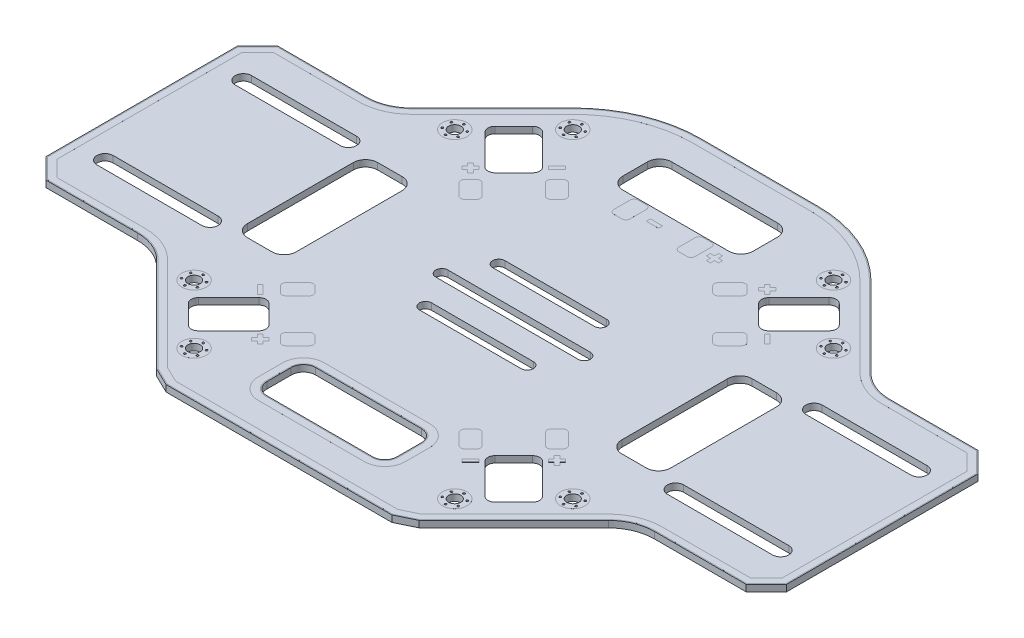
SolidWorks part; units mm, degrees
material "Baseplate Screw Material"
ref_plane "Front Plane" through (0, 0, 0) normal (0, 0, 1) x (1, 0, 0)
ref_plane "Top Plane" through (0, 0, 0) normal (0, 1, 0) x (1, 0, 0)
ref_plane "Right Plane" through (0, 0, 0) normal (1, 0, 0) x (0, 0, -1)
sketch "Sketch1" plane through (0, 0, 0) normal (0, 1, 0) x (1, 0, 0)
  line L0 (0, 60.3186) -> (0, -57.6814) construction
  line L1 (-27.75, -57.6814) -> (27.75, -57.6814)
  line L2 (-13, -47.6814) -> (13, -47.6814)
  line L3 (-16, -38.6814) -> (-16, -44.6814)
  line L4 (16, -38.6814) -> (16, -44.6814)
  line L5 (-16, -41.6814) -> (16, -41.6814) construction
  line L6 (-13, -35.6814) -> (13, -35.6814)
  line L7 (-27.75, -57.6814) -> (-32.25, -55.502)
  line L8 (27.75, -57.6814) -> (32.25, -55.502)
  line L9 (-32.25, -55.502) -> (32.25, -55.502) construction
  line L10 (32.25, -55.502) -> (55.502, -32.25)
  line L11 (-32.25, -55.502) -> (-55.502, -32.25)
  line L12 (-43.876, 43.876) -> (43.876, -43.876) construction
  line L13 (-43.876, -43.876) -> (43.876, 43.876) construction
  line L14 (37.6888, -42.285) -> (42.285, -37.6888)
  line L15 (27.7893, -34.8604) -> (35.2139, -42.285)
  line L16 (34.8604, -27.7893) -> (42.285, -35.2139)
  line L17 (31.5016, -38.5727) -> (38.5727, -31.5016) construction
  line L18 (27.7893, -32.3855) -> (32.3855, -27.7893)
  line L19 (-38.5727, -31.5016) -> (-31.5016, -38.5727) construction
  line L20 (-35.2139, -42.285) -> (-27.7893, -34.8604)
  line L21 (-42.285, -35.2139) -> (-34.8604, -27.7893)
  line L22 (-32.3855, -27.7893) -> (-27.7893, -32.3855)
  line L23 (-42.285, -37.6888) -> (-37.6888, -42.285)
  line L24 (-63.5, -28.9371) -> (63.5, -28.9371) construction
  line L25 (63.5, -28.9371) -> (86, -28.9371)
  line L26 (-63.5, -28.9371) -> (-86, -28.9371)
  line L27 (-91, -23.9371) -> (-91, 23.0629)
  line L28 (91, -23.9371) -> (91, 23.0629)
  line L29 (-86, -28.9371) -> (-86, 28.0629) construction
  line L30 (86, -28.9371) -> (86, 28.0629) construction
  line L31 (-91, -0.4371) -> (-86, -0.4371) construction
  line L32 (86, -0.4371) -> (91, -0.4371) construction
  line L33 (86, -28.9371) -> (91, -23.9371)
  line L34 (-91, -23.9371) -> (-86, -28.9371)
  line L35 (91, 23.0629) -> (86, 28.0629)
  line L36 (-91, 23.0629) -> (-86, 28.0629)
  line L37 (-56.4271, 31.3248) -> (-36.6281, 51.1238)
  line L38 (36.6281, 51.1238) -> (56.4271, 31.3248)
  line L39 (-35.2139, 42.285) -> (-27.7893, 34.8604)
  line L40 (-36.6281, 51.1238) -> (-27.7893, 42.285) construction
  line L41 (-27.7893, 42.285) -> (-31.5016, 38.5727) construction
  line L42 (-42.285, 35.2139) -> (-34.8604, 27.7893)
  line L43 (-31.5016, 38.5727) -> (-38.5727, 31.5016) construction
  line L44 (-42.285, 37.6888) -> (-37.6888, 42.285)
  line L45 (-32.3855, 27.7893) -> (-27.7893, 32.3855)
  line L46 (-86, 28.0629) -> (-64.3021, 28.0629)
  line L47 (86, 28.0629) -> (64.3021, 28.0629)
  line L48 (37.6888, 42.285) -> (42.285, 37.6888)
  line L49 (27.7893, 32.3855) -> (32.3855, 27.7893)
  line L50 (27.7893, 34.8604) -> (35.2139, 42.285)
  line L51 (34.8604, 27.7893) -> (42.285, 35.2139)
  line L52 (31.5016, 38.5727) -> (38.5727, 31.5016) construction
  line L53 (31.5016, 38.5727) -> (27.7893, 42.285) construction
  line L54 (27.7893, 42.285) -> (36.6281, 51.1238) construction
  line L55 (-14.43, 60.3186) -> (14.43, 60.3186)
  line L56 (-13, 51.8186) -> (13, 51.8186)
  line L57 (-13, 39.8186) -> (13, 39.8186)
  line L58 (16, 48.8186) -> (16, 42.8186)
  line L59 (-16, 48.8186) -> (-16, 42.8186)
  line L60 (-12.5, -10.6814) -> (12.5, -10.6814)
  line L61 (-12.5, -7.6814) -> (12.5, -7.6814)
  line L62 (-17.5, -1.6814) -> (17.5, -1.6814)
  line L63 (-17.5, 1.3186) -> (17.5, 1.3186)
  line L64 (-12.5, 7.3186) -> (12.5, 7.3186)
  line L65 (-12.5, 10.3186) -> (12.5, 10.3186)
  line L66 (-52, 12.5629) -> (-52, -13.4371)
  line L67 (-86, -0.4371) -> (-52, -0.4371) construction
  line L68 (-40, 12.5629) -> (-40, -13.4371)
  line L69 (52, 12.5629) -> (52, -13.4371)
  line L70 (-49, 15.5629) -> (-43, 15.5629)
  line L71 (-49, -16.4371) -> (-43, -16.4371)
  line L72 (86, -0.4371) -> (52, -0.4371) construction
  line L73 (40, 12.5629) -> (40, -13.4371)
  line L74 (43, 15.5629) -> (49, 15.5629)
  line L75 (43, -16.4371) -> (49, -16.4371)
  line L76 (-83, 18.5629) -> (-57.2, 18.5629)
  line L77 (-83, 14.5629) -> (-57.2, 14.5629)
  line L78 (-83, -15.4371) -> (-57.2, -15.4371)
  line L79 (-83, -19.4371) -> (-57.2, -19.4371)
  line L80 (57.2, -15.4371) -> (83, -15.4371)
  line L81 (57.2, -19.4371) -> (83, -19.4371)
  line L82 (57.2, 18.5629) -> (83, 18.5629)
  line L83 (57.2, 14.5629) -> (83, 14.5629)
  line L84 (-46.5276, 32.0319) -> (-32.0319, 46.5276) construction
  line L85 (32.0319, -46.5276) -> (46.5276, -32.0319) construction
  arc A0 (-16, -44.6814) -> (-13, -47.6814) centre (-13, -44.6814) ccw
  arc A1 (-13, -35.6814) -> (-16, -38.6814) centre (-13, -38.6814) ccw
  arc A2 (16, -38.6814) -> (13, -35.6814) centre (13, -38.6814) ccw
  arc A3 (13, -47.6814) -> (16, -44.6814) centre (13, -44.6814) ccw
  arc A4 (27.7893, -32.3855) -> (27.7893, -34.8604) centre (29.0267, -33.6229) ccw
  arc A5 (34.8604, -27.7893) -> (32.3855, -27.7893) centre (33.6229, -29.0267) ccw
  arc A6 (35.2139, -42.285) -> (37.6888, -42.285) centre (36.4514, -41.0475) ccw
  arc A7 (42.285, -37.6888) -> (42.285, -35.2139) centre (41.0475, -36.4514) ccw
  arc A8 (-37.6888, -42.285) -> (-35.2139, -42.285) centre (-36.4514, -41.0475) ccw
  arc A9 (-42.285, -35.2139) -> (-42.285, -37.6888) centre (-41.0475, -36.4514) ccw
  arc A10 (-32.3855, -27.7893) -> (-34.8604, -27.7893) centre (-33.6229, -29.0267) ccw
  arc A11 (-27.7893, -34.8604) -> (-27.7893, -32.3855) centre (-29.0267, -33.6229) ccw
  arc A12 (-55.502, -32.25) -> (-63.5, -28.9371) centre (-63.5, -40.248) ccw
  arc A13 (63.5, -28.9371) -> (55.502, -32.25) centre (63.5, -40.248) ccw
  arc A14 (-42.285, 37.6888) -> (-42.285, 35.2139) centre (-41.0475, 36.4514) ccw
  arc A15 (-35.2139, 42.285) -> (-37.6888, 42.285) centre (-36.4514, 41.0475) ccw
  arc A16 (-27.7893, 32.3855) -> (-27.7893, 34.8604) centre (-29.0267, 33.6229) ccw
  arc A17 (-34.8604, 27.7893) -> (-32.3855, 27.7893) centre (-33.6229, 29.0267) ccw
  arc A18 (-64.3021, 28.0629) -> (-56.4271, 31.3248) centre (-64.3021, 39.1998) ccw
  arc A19 (56.4271, 31.3248) -> (64.3021, 28.0629) centre (64.3021, 39.1998) ccw
  arc A20 (27.7893, 34.8604) -> (27.7893, 32.3855) centre (29.0267, 33.6229) ccw
  arc A21 (37.6888, 42.285) -> (35.2139, 42.285) centre (36.4514, 41.0475) ccw
  arc A22 (42.285, 35.2139) -> (42.285, 37.6888) centre (41.0475, 36.4514) ccw
  arc A23 (32.3855, 27.7893) -> (34.8604, 27.7893) centre (33.6229, 29.0267) ccw
  arc A24 (-14.43, 60.3186) -> (-36.6281, 51.1238) centre (-14.43, 28.9257) ccw
  arc A25 (13, 39.8186) -> (16, 42.8186) centre (13, 42.8186) ccw
  arc A26 (36.6281, 51.1238) -> (14.43, 60.3186) centre (14.43, 28.9257) ccw
  arc A27 (16, 48.8186) -> (13, 51.8186) centre (13, 48.8186) ccw
  arc A28 (-16, 42.8186) -> (-13, 39.8186) centre (-13, 42.8186) ccw
  arc A29 (-13, 51.8186) -> (-16, 48.8186) centre (-13, 48.8186) ccw
  arc A30 (-12.5, -7.6814) -> (-12.5, -10.6814) centre (-12.5, -9.1814) ccw
  arc A31 (12.5, -10.6814) -> (12.5, -7.6814) centre (12.5, -9.1814) ccw
  arc A32 (-17.5, 1.3186) -> (-17.5, -1.6814) centre (-17.5, -0.1814) ccw
  arc A33 (17.5, -1.6814) -> (17.5, 1.3186) centre (17.5, -0.1814) ccw
  arc A34 (-12.5, 10.3186) -> (-12.5, 7.3186) centre (-12.5, 8.8186) ccw
  arc A35 (12.5, 7.3186) -> (12.5, 10.3186) centre (12.5, 8.8186) ccw
  arc A36 (-49, 15.5629) -> (-52, 12.5629) centre (-49, 12.5629) ccw
  arc A37 (-40, 12.5629) -> (-43, 15.5629) centre (-43, 12.5629) ccw
  arc A38 (-52, -13.4371) -> (-49, -16.4371) centre (-49, -13.4371) ccw
  arc A39 (-43, -16.4371) -> (-40, -13.4371) centre (-43, -13.4371) ccw
  arc A40 (43, 15.5629) -> (40, 12.5629) centre (43, 12.5629) ccw
  arc A41 (52, 12.5629) -> (49, 15.5629) centre (49, 12.5629) ccw
  arc A42 (40, -13.4371) -> (43, -16.4371) centre (43, -13.4371) ccw
  arc A43 (49, -16.4371) -> (52, -13.4371) centre (49, -13.4371) ccw
  arc A44 (-57.2, 14.5629) -> (-57.2, 18.5629) centre (-57.2, 16.5629) ccw
  arc A45 (-83, 18.5629) -> (-83, 14.5629) centre (-83, 16.5629) ccw
  arc A46 (-83, -15.4371) -> (-83, -19.4371) centre (-83, -17.4371) ccw
  arc A47 (-57.2, -19.4371) -> (-57.2, -15.4371) centre (-57.2, -17.4371) ccw
  arc A48 (57.2, -15.4371) -> (57.2, -19.4371) centre (57.2, -17.4371) ccw
  arc A49 (83, -19.4371) -> (83, -15.4371) centre (83, -17.4371) ccw
  arc A50 (57.2, 18.5629) -> (57.2, 14.5629) centre (57.2, 16.5629) ccw
  arc A51 (83, 14.5629) -> (83, 18.5629) centre (83, 16.5629) ccw
  circle A52 centre (-32.0319, 46.5276) radius 1.5
  circle A53 centre (-46.5276, 32.0319) radius 1.5
  circle A54 centre (32.0319, -46.5276) radius 1.5
  circle A55 centre (46.5276, -32.0319) radius 1.5
  circle A56 centre (-46.5276, -32.0319) radius 1.5
  circle A57 centre (-32.0319, -46.5276) radius 1.5
  circle A58 centre (32.0319, 46.5276) radius 1.5
  circle A59 centre (46.5276, 32.0319) radius 1.5
  point P4 (-35.0371, 35.0371)
  point P5 (0, -47.6814)
  point P14 (0, -41.6814)
  point P15 (0, -35.6814)
  point P19 (0, -55.502)
  point P29 (0, 0)
  point P30 (39.9869, -39.9869)
  point P32 (0, 0)
  point P42 (30.0874, -30.0874)
  point P43 (35.0371, -35.0371)
  point P50 (-35.0371, -35.0371)
  point P53 (-38.5727, -31.5016)
  point P62 (-39.9869, -39.9869)
  point P63 (-30.0874, -30.0874)
  point P70 (0, -28.9371)
  point P99 (-39.9869, 39.9869)
  point P102 (-30.0874, 30.0874)
  point P119 (35.0371, 35.0371)
  point P122 (39.9869, 39.9869)
  point P123 (30.0874, 30.0874)
  point P135 (0, 51.8186)
  point P138 (0, 39.8186)
  point P147 (0, -10.6814)
  point P151 (-14, -9.1814)
  point P153 (14, -9.1814)
  point P156 (0, -1.6814)
  point P158 (-19, -0.1814)
  point P162 (19, -0.1814)
  point P167 (0, 7.3186)
  point P203 (-85, 16.5629)
  point P205 (-55.2, 16.5629)
  point P217 (85, -17.4371)
  point P229 (-39.2798, 39.2798)
  point P232 (39.2798, -39.2798)
  dimension "D5" = 12
  dimension "D6" = 55.5
  dimension "D14" = 14
  dimension "D15" = 127
  dimension "D16" = 22.5
  dimension "D23" = 8.5
  dimension "D24" = 25
  dimension "D25" = 3
  dimension "D28" = 3
  dimension "D31" = 39
  dimension "D32" = 9.5
  dimension "D34" = 29.8
  dimension "D38" = 6
  dimension "D39" = 3
  dimension "D1" = 118
  dimension "D2" = 10
  dimension "D3" = 32
  dimension "D4" = 6
  dimension "D7" = 64.5
  dimension "D8" = 5
  dimension "D9" = 124.1
  dimension "D10" = 45
  dimension "D11" = 5.5
  dimension "D12" = 6.5
  dimension "D13" = 10
  dimension "D17" = 22.5
  dimension "D18" = 5
  dimension "D19" = 45
  dimension "D20" = 47
  dimension "D21" = 28
  dimension "D22" = 5.25
  dimension "D26" = 28
  dimension "D27" = 6
  dimension "D29" = 38
  dimension "D30" = 6
  dimension "D33" = 4
  dimension "D35" = 6
  dimension "D36" = 9.5
  dimension "D37" = 4
  dimension "D40" = 6.5
  dimension "D41" = 6.5
extrude "Boss-Extrude1" add sketch "Sketch1" along normal blind 0.8 and the other way blind 0.8
sketch "Sketch2" plane through (0, 0.8, 0) normal (0, 1, 0) x (1, 0, 0)
  line L0 (-27.6926, -57.4314) -> (27.6926, -57.4314)
  line L1 (-27.75, -57.6814) -> (27.75, -57.6814) construction
  line L2 (-27.6926, -57.4314) -> (-32.1031, -55.2953)
  line L3 (-32.25, -55.502) -> (-27.75, -57.6814) construction
  line L4 (27.6926, -57.4314) -> (32.1031, -55.2953)
  line L5 (27.75, -57.6814) -> (32.25, -55.502) construction
  line L6 (0, -57.6814) -> (0, -57.4314) construction
  line L7 (-32.1031, -55.2953) -> (-55.3252, -32.0732)
  line L8 (-55.502, -32.25) -> (-32.25, -55.502) construction
  line L9 (32.1031, -55.2953) -> (55.3252, -32.0732)
  line L10 (32.25, -55.502) -> (55.502, -32.25) construction
  line L11 (-85.8964, -28.6871) -> (-63.5, -28.6871)
  line L12 (-85.8964, -28.6871) -> (-90.75, -23.8335)
  line L13 (-91, -23.9371) -> (-86, -28.9371) construction
  line L14 (-86, -28.9371) -> (-63.5, -28.9371) construction
  line L15 (63.5, -28.6871) -> (85.8964, -28.6871)
  line L16 (85.8964, -28.6871) -> (90.75, -23.8335)
  line L17 (-90.75, -23.8335) -> (-90.75, 22.9593)
  line L18 (-91, 23.0629) -> (-91, -23.9371) construction
  line L19 (-90.75, 22.9593) -> (-85.8964, 27.8129)
  line L20 (-85.8964, 27.8129) -> (-64.3021, 27.8129)
  line L21 (-64.3021, 28.0629) -> (-86, 28.0629) construction
  line L22 (-56.2503, 31.1481) -> (-36.4514, 50.947)
  line L23 (-36.6281, 51.1238) -> (-56.4271, 31.3248) construction
  line L24 (-14.43, 60.0686) -> (14.43, 60.0686)
  line L25 (14.43, 60.3186) -> (-14.43, 60.3186) construction
  line L26 (56.2503, 31.1481) -> (36.4514, 50.947)
  line L27 (56.4271, 31.3248) -> (36.6281, 51.1238) construction
  line L28 (64.3021, 27.8129) -> (85.8964, 27.8129)
  line L29 (86, 28.0629) -> (64.3021, 28.0629) construction
  line L30 (85.8964, 27.8129) -> (90.75, 22.9593)
  line L31 (91, 23.0629) -> (86, 28.0629) construction
  line L32 (90.75, 22.9593) -> (90.75, -23.8335)
  line L33 (-55.0836, 29.9813) -> (-35.2846, 49.7803)
  line L34 (-14.43, 58.4186) -> (14.43, 58.4186)
  line L35 (55.0836, 29.9813) -> (35.2846, 49.7803)
  line L36 (64.3021, 26.1629) -> (85.213, 26.1629)
  line L37 (85.213, 26.1629) -> (89.1, 22.2759)
  line L38 (89.1, 22.2759) -> (89.1, -23.1501)
  line L39 (85.213, -27.0371) -> (89.1, -23.1501)
  line L40 (63.5, -27.0371) -> (85.213, -27.0371)
  line L41 (31.1332, -53.9317) -> (54.1584, -30.9065)
  line L42 (27.3141, -55.7814) -> (31.1332, -53.9317)
  line L43 (-27.3141, -55.7814) -> (27.3141, -55.7814)
  line L44 (-27.3141, -55.7814) -> (-31.1332, -53.9317)
  line L45 (-31.1332, -53.9317) -> (-54.1584, -30.9065)
  line L46 (-85.213, -27.0371) -> (-63.5, -27.0371)
  line L47 (-85.213, -27.0371) -> (-89.1, -23.1501)
  line L48 (-89.1, -23.1501) -> (-89.1, 22.2759)
  line L49 (-89.1, 22.2759) -> (-85.213, 26.1629)
  line L50 (-85.213, 26.1629) -> (-64.3021, 26.1629)
  line L51 (-13, -35.4314) -> (13, -35.4314)
  line L52 (-16.25, -38.6814) -> (-16.25, -44.6814)
  line L53 (-13, -47.9314) -> (13, -47.9314)
  line L54 (16.25, -44.6814) -> (16.25, -38.6814)
  line L55 (16, -44.6814) -> (16, -38.6814) construction
  line L56 (13, -35.6814) -> (-13, -35.6814) construction
  line L57 (-16, -38.6814) -> (-16, -44.6814) construction
  line L58 (-13, -47.6814) -> (13, -47.6814) construction
  line L59 (-13, -33.6314) -> (13, -33.6314)
  line L60 (18.05, -44.6814) -> (18.05, -38.6814)
  line L61 (-13, -49.7314) -> (13, -49.7314)
  line L62 (-18.05, -38.6814) -> (-18.05, -44.6814)
  line L63 (32.0319, -43.5276) -> (32.0319, -44.2776) construction
  line L64 (-32.0319, -44.2776) -> (-33.9805, -45.4026) construction
  line L65 (-33.9805, -45.4026) -> (-33.9805, -47.6526) construction
  line L66 (-33.9805, -47.6526) -> (-32.0319, -48.7776) construction
  line L67 (-32.0319, -48.7776) -> (-30.0834, -47.6526) construction
  line L68 (-30.0834, -47.6526) -> (-30.0834, -45.4026) construction
  line L69 (-30.0834, -45.4026) -> (-32.0319, -44.2776) construction
  line L70 (-46.5276, -29.7819) -> (-48.4762, -30.9069) construction
  line L71 (-48.4762, -30.9069) -> (-48.4762, -33.1569) construction
  line L72 (-48.4762, -33.1569) -> (-46.5276, -34.2819) construction
  line L73 (-46.5276, -34.2819) -> (-44.5791, -33.1569) construction
  line L74 (-44.5791, -33.1569) -> (-44.5791, -30.9069) construction
  line L75 (-44.5791, -30.9069) -> (-46.5276, -29.7819) construction
  line L76 (-46.5276, 34.2819) -> (-48.4762, 33.1569) construction
  line L77 (-48.4762, 33.1569) -> (-48.4762, 30.9069) construction
  line L78 (-48.4762, 30.9069) -> (-46.5276, 29.7819) construction
  line L79 (-46.5276, 29.7819) -> (-44.5791, 30.9069) construction
  line L80 (-44.5791, 30.9069) -> (-44.5791, 33.1569) construction
  line L81 (-44.5791, 33.1569) -> (-46.5276, 34.2819) construction
  line L82 (-32.0319, 48.7776) -> (-33.9805, 47.6526) construction
  line L83 (-33.9805, 47.6526) -> (-33.9805, 45.4026) construction
  line L84 (-33.9805, 45.4026) -> (-32.0319, 44.2776) construction
  line L85 (-32.0319, 44.2776) -> (-30.0834, 45.4026) construction
  line L86 (-30.0834, 45.4026) -> (-30.0834, 47.6526) construction
  line L87 (-30.0834, 47.6526) -> (-32.0319, 48.7776) construction
  line L88 (32.0319, 48.7776) -> (30.0834, 47.6526) construction
  line L89 (30.0834, 47.6526) -> (30.0834, 45.4026) construction
  line L90 (30.0834, 45.4026) -> (32.0319, 44.2776) construction
  line L91 (32.0319, 44.2776) -> (33.9805, 45.4026) construction
  line L92 (33.9805, 45.4026) -> (33.9805, 47.6526) construction
  line L93 (33.9805, 47.6526) -> (32.0319, 48.7776) construction
  line L94 (46.5276, 34.2819) -> (44.5791, 33.1569) construction
  line L95 (44.5791, 33.1569) -> (44.5791, 30.9069) construction
  line L96 (44.5791, 30.9069) -> (46.5276, 29.7819) construction
  line L97 (46.5276, 29.7819) -> (48.4762, 30.9069) construction
  line L98 (48.4762, 30.9069) -> (48.4762, 33.1569) construction
  line L99 (48.4762, 33.1569) -> (46.5276, 34.2819) construction
  line L100 (46.5276, -29.7819) -> (44.5791, -30.9069) construction
  line L101 (44.5791, -30.9069) -> (44.5791, -33.1569) construction
  line L102 (44.5791, -33.1569) -> (46.5276, -34.2819) construction
  line L103 (46.5276, -34.2819) -> (48.4762, -33.1569) construction
  line L104 (48.4762, -33.1569) -> (48.4762, -30.9069) construction
  line L105 (48.4762, -30.9069) -> (46.5276, -29.7819) construction
  line L106 (32.0319, -44.2776) -> (30.0834, -45.4026) construction
  line L107 (30.0834, -45.4026) -> (30.0834, -47.6526) construction
  line L108 (30.0834, -47.6526) -> (32.0319, -48.7776) construction
  line L109 (32.0319, -48.7776) -> (33.9805, -47.6526) construction
  line L110 (33.9805, -47.6526) -> (33.9805, -45.4026) construction
  line L111 (33.9805, -45.4026) -> (32.0319, -44.2776) construction
  line L112 (32.0319, -44.2776) -> (32.0319, -45.0276) construction
  arc A0 (-55.3252, -32.0732) -> (-63.5, -28.6871) centre (-63.5, -40.248) ccw
  arc A1 (-55.502, -32.25) -> (-63.5, -28.9371) centre (-63.5, -40.248) ccw construction
  arc A2 (63.5, -28.6871) -> (55.3252, -32.0732) centre (63.5, -40.248) ccw
  arc A3 (63.5, -28.9371) -> (55.502, -32.25) centre (63.5, -40.248) ccw construction
  arc A4 (-64.3021, 27.8129) -> (-56.2503, 31.1481) centre (-64.3021, 39.1998) ccw
  arc A5 (-64.3021, 28.0629) -> (-56.4271, 31.3248) centre (-64.3021, 39.1998) ccw construction
  arc A6 (-14.43, 60.0686) -> (-36.4514, 50.947) centre (-14.43, 28.9257) ccw
  arc A7 (-14.43, 60.3186) -> (-36.6281, 51.1238) centre (-14.43, 28.9257) ccw construction
  arc A8 (36.4514, 50.947) -> (14.43, 60.0686) centre (14.43, 28.9257) ccw
  arc A9 (36.6281, 51.1238) -> (14.43, 60.3186) centre (14.43, 28.9257) ccw construction
  arc A10 (56.2503, 31.1481) -> (64.3021, 27.8129) centre (64.3021, 39.1998) ccw
  arc A11 (56.4271, 31.3248) -> (64.3021, 28.0629) centre (64.3021, 39.1998) ccw construction
  arc A12 (-14.43, 58.4186) -> (-35.2846, 49.7803) centre (-14.43, 28.9257) ccw
  arc A13 (35.2846, 49.7803) -> (14.43, 58.4186) centre (14.43, 28.9257) ccw
  arc A14 (55.0836, 29.9813) -> (64.3021, 26.1629) centre (64.3021, 39.1998) ccw
  arc A15 (63.5, -27.0371) -> (54.1584, -30.9065) centre (63.5, -40.248) ccw
  arc A16 (-54.1584, -30.9065) -> (-63.5, -27.0371) centre (-63.5, -40.248) ccw
  arc A17 (-64.3021, 26.1629) -> (-55.0836, 29.9813) centre (-64.3021, 39.1998) ccw
  arc A18 (-13, -35.4314) -> (-16.25, -38.6814) centre (-13, -38.6814) ccw
  arc A19 (16.25, -38.6814) -> (13, -35.4314) centre (13, -38.6814) ccw
  arc A20 (-16.25, -44.6814) -> (-13, -47.9314) centre (-13, -44.6814) ccw
  arc A21 (13, -47.9314) -> (16.25, -44.6814) centre (13, -44.6814) ccw
  arc A22 (-13, -35.6814) -> (-16, -38.6814) centre (-13, -38.6814) ccw construction
  arc A23 (-16, -44.6814) -> (-13, -47.6814) centre (-13, -44.6814) ccw construction
  arc A24 (16, -38.6814) -> (13, -35.6814) centre (13, -38.6814) ccw construction
  arc A25 (13, -47.6814) -> (16, -44.6814) centre (13, -44.6814) ccw construction
  arc A26 (18.05, -38.6814) -> (13, -33.6314) centre (13, -38.6814) ccw
  arc A27 (13, -49.7314) -> (18.05, -44.6814) centre (13, -44.6814) ccw
  arc A28 (-18.05, -44.6814) -> (-13, -49.7314) centre (-13, -44.6814) ccw
  arc A29 (-13, -33.6314) -> (-18.05, -38.6814) centre (-13, -38.6814) ccw
  circle A30 centre (-32.0319, -46.5276) radius 1.5
  circle A31 centre (-46.5276, -32.0319) radius 1.5
  circle A32 centre (-46.5276, 32.0319) radius 1.5
  circle A33 centre (-32.0319, 46.5276) radius 1.5
  circle A34 centre (32.0319, 46.5276) radius 1.5
  circle A35 centre (46.5276, 32.0319) radius 1.5
  circle A36 centre (46.5276, -32.0319) radius 1.5
  circle A37 centre (32.0319, -46.5276) radius 1.5
  circle A38 centre (-32.0319, -46.5276) radius 1.5 construction
  circle A39 centre (-46.5276, -32.0319) radius 1.5 construction
  circle A40 centre (-46.5276, 32.0319) radius 1.5 construction
  circle A41 centre (-32.0319, 46.5276) radius 1.5 construction
  circle A42 centre (32.0319, 46.5276) radius 1.5 construction
  circle A43 centre (46.5276, 32.0319) radius 1.5 construction
  circle A44 centre (46.5276, -32.0319) radius 1.5 construction
  circle A45 centre (32.0319, -46.5276) radius 1.5 construction
  circle A46 centre (-32.0319, -46.5276) radius 3
  circle A47 centre (-46.5276, -32.0319) radius 3
  circle A48 centre (-46.5276, 32.0319) radius 3
  circle A49 centre (-32.0319, 46.5276) radius 3
  circle A50 centre (32.0319, 46.5276) radius 3
  circle A51 centre (46.5276, 32.0319) radius 3
  circle A52 centre (46.5276, -32.0319) radius 3
  circle A53 centre (32.0319, -46.5276) radius 3
  circle A54 centre (-32.0319, -46.5276) radius 1.9486 construction
  circle A55 centre (-46.5276, -32.0319) radius 1.9486 construction
  circle A56 centre (-46.5276, 32.0319) radius 1.9486 construction
  circle A57 centre (-32.0319, 46.5276) radius 1.9486 construction
  circle A58 centre (32.0319, 46.5276) radius 1.9486 construction
  circle A59 centre (46.5276, 32.0319) radius 1.9486 construction
  circle A60 centre (46.5276, -32.0319) radius 1.9486 construction
  circle A61 centre (32.0319, -46.5276) radius 1.9486 construction
  circle A62 centre (32.0319, -44.2776) radius 0.25
  circle A63 centre (33.9805, -45.4026) radius 0.25
  circle A64 centre (33.9805, -47.6526) radius 0.25
  circle A65 centre (32.0319, -48.7776) radius 0.25
  circle A66 centre (30.0834, -47.6526) radius 0.25
  circle A67 centre (30.0834, -45.4026) radius 0.25
  circle A68 centre (46.5276, -34.2819) radius 0.25
  circle A69 centre (48.4762, -33.1569) radius 0.25
  circle A70 centre (48.4762, -30.9069) radius 0.25
  circle A71 centre (46.5276, -29.7819) radius 0.25
  circle A72 centre (44.5791, -30.9069) radius 0.25
  circle A73 centre (44.5791, -33.1569) radius 0.25
  circle A74 centre (46.5276, 29.7819) radius 0.25
  circle A75 centre (48.4762, 30.9069) radius 0.25
  circle A76 centre (48.4762, 33.1569) radius 0.25
  circle A77 centre (46.5276, 34.2819) radius 0.25
  circle A78 centre (44.5791, 33.1569) radius 0.25
  circle A79 centre (44.5791, 30.9069) radius 0.25
  circle A80 centre (32.0319, 44.2776) radius 0.25
  circle A81 centre (33.9805, 45.4026) radius 0.25
  circle A82 centre (33.9805, 47.6526) radius 0.25
  circle A83 centre (32.0319, 48.7776) radius 0.25
  circle A84 centre (30.0834, 47.6526) radius 0.25
  circle A85 centre (30.0834, 45.4026) radius 0.25
  circle A86 centre (-32.0319, 48.7776) radius 0.25
  circle A87 centre (-30.0834, 47.6526) radius 0.25
  circle A88 centre (-30.0834, 45.4026) radius 0.25
  circle A89 centre (-32.0319, 44.2776) radius 0.25
  circle A90 centre (-33.9805, 47.6526) radius 0.25
  circle A91 centre (-33.9805, 45.4026) radius 0.25
  circle A92 centre (-46.5276, 29.7819) radius 0.25
  circle A93 centre (-44.5791, 30.9069) radius 0.25
  circle A94 centre (-44.5791, 33.1569) radius 0.25
  circle A95 centre (-46.5276, 34.2819) radius 0.25
  circle A96 centre (-48.4762, 33.1569) radius 0.25
  circle A97 centre (-48.4762, 30.9069) radius 0.25
  circle A98 centre (-46.5276, -29.7819) radius 0.25
  circle A99 centre (-44.5791, -30.9069) radius 0.25
  circle A100 centre (-44.5791, -33.1569) radius 0.25
  circle A101 centre (-46.5276, -34.2819) radius 0.25
  circle A102 centre (-48.4762, -33.1569) radius 0.25
  circle A103 centre (-48.4762, -30.9069) radius 0.25
  circle A104 centre (-32.0319, -44.2776) radius 0.25
  circle A105 centre (-30.0834, -45.4026) radius 0.25
  circle A106 centre (-30.0834, -47.6526) radius 0.25
  circle A107 centre (-32.0319, -48.7776) radius 0.25
  circle A108 centre (-33.9805, -47.6526) radius 0.25
  circle A109 centre (-33.9805, -45.4026) radius 0.25
  dimension "D2" = 0.25
  dimension "D5" = 0.25
  dimension "D7" = 1.65
  dimension "D8" = 0.25
  dimension "D10" = 6
  dimension "D11" = 0.5
  dimension "D1" = 0.25
  dimension "D3" = 0.25
  dimension "D4" = 0.25
  dimension "D6" = 0.25
  dimension "D9" = 1.8
extrude "Boss-Extrude2" add sketch "Sketch2" along normal blind 0.001 contours A10 L26 A8 L24 A6 L22 A4 L20 L19 L17 L12 L11 A0 L7 L2 L0 L4 L9 A2 L15 L16 L32 L30 L28 L50 A17 L33 A12 L34 A13 L35 A14 L36 L37 L38 L39 L40 A15 L41 L42 L43 L44 L45 A16 L46 L47 L48 L49 | A46 A109 A108 A107 A106 A105 A104 A30 | A47 A103 A102 A101 A100 A99 A98 A31 | A48 A97 A96 A95 A94 A93 A92 A32 | A49 A91 A90 A89 A88 A87 A86 A33 | A50 A85 A84 A83 A82 A81 A80 A34 | A51 A79 A78 A77 A76 A75 A74 A35 | A52 A73 A72 A71 A70 A69 A68 A36 | A53 A67 A66 A65 A64 A63 A62 A37 | L59 A29 L62 A28 L61 A27 L60 A26 A21 L53 A20 L52 A18 L51 A19 L54 region at (-29.8036, 0.8, 56.1688) region at (0, 0.8, 34.0267) region at (-34.9471, 0.8, 46.5276) region at (-49.4428, 0.8, 32.0319) region at (-49.4428, 0.8, -32.0319) region at (-34.9471, 0.8, -46.5276) region at (29.1168, 0.8, -46.5276) region at (43.6125, 0.8, -32.0319) region at (43.6125, 0.8, 32.0319) region at (29.1168, 0.8, 46.5276)
mirror "Mirror1" about plane through (0, 0, 0) normal (0, 1, 0) of "Boss-Extrude2"
sketch "Sketch3" plane through (0, -0.8, 0) normal (0, -1, 0) x (1, 0, 0)
  line L0 (0, 49.7314) -> (0, 51.7314) construction
  line L1 (-13, 49.7314) -> (13, 49.7314) construction
  line L2 (-27.3141, 55.7814) -> (27.3141, 55.7814) construction
  line L3 (11, 51.7314) -> (-11, 51.7314) construction
  line L4 (11, 53.7814) -> (-11, 53.7814) construction
  line L5 (0, 53.7814) -> (0, 55.7814) construction
  line L6 (11, 51.7314) -> (11, 53.7814) construction
  line L7 (-11, 51.7314) -> (-11, 53.7814) construction
  line L8 (11.29, 53.7814) -> (-10.71, 53.7814) construction
  text T0 "<b>DJI INNOVATIONS</b>" font "@Adobe Heiti Std R" height 2.05
  point P8 (0, 51.7314)
  point P11 (0, 53.7814)
  dimension "D1" = 2
  dimension "D2" = 22
  dimension "D3" = 0.29
extrude "Boss-Extrude3" add sketch "Sketch3" along normal blind 0.001
sketch "Sketch4" plane through (0, -0.8, 0) normal (0, -1, 0) x (1, 0, 0)
  line L0 (9.1282, 51.7314) -> (9.1282, 51.9909)
  line L1 (9.1282, 51.9909) -> (8.7389, 51.9909)
  line L2 (8.7389, 51.9909) -> (8.7389, 51.7314)
  line L3 (9.1282, 51.7314) -> (8.4275, 51.7314) construction
  line L4 (8.7389, 51.7314) -> (9.1282, 51.7314)
  line L6 (-3.2442, 51.7314) -> (-3.2442, 52.0168)
  line L7 (-3.2442, 52.0168) -> (-3.3442, 52.0168)
  line L8 (-3.893, 52.0168) -> (-3.2442, 52.0168) construction
  line L9 (-3.3442, 52.0168) -> (-3.3442, 51.7314)
  line L10 (-3.2442, 51.7314) -> (-4.8531, 51.7314) construction
  line L11 (-3.3442, 51.7314) -> (-3.2442, 51.7314)
  line L12 (-4.8531, 51.7314) -> (-4.7531, 51.7314)
  line L13 (-4.7531, 51.7314) -> (-4.7531, 52.0168)
  line L14 (-4.8531, 52.0168) -> (-4.2044, 52.0168) construction
  line L15 (-4.7531, 52.0168) -> (-4.8531, 52.0168)
  line L16 (-4.8531, 52.0168) -> (-4.8531, 51.7314)
  dimension "D1" = 0.1
extrude "Cut-Extrude1" cut sketch "Sketch4" along normal up to surface (0.001 mm away) up to face at (8.9409, -0.801, 52.931)
sketch "Sketch5" plane through (0, 0.8, 0) normal (0, 1, 0) x (1, 0, 0)
  line L0 (35.7442, -27.259) -> (36.4514, -26.5519)
  line L1 (35.0371, -26.5519) -> (35.7442, -25.8448)
  line L2 (35.3907, -26.9054) -> (37.512, -24.7841) construction
  line L3 (35.0371, -26.5519) -> (35.7442, -27.259)
  line L4 (37.1585, -24.4305) -> (37.8656, -25.1376)
  line L5 (42.285, -35.2139) -> (34.8604, -27.7893) construction
  line L6 (32.1031, -55.2953) -> (55.3252, -32.0732) construction
  line L8 (35.3907, -24.7841) -> (37.512, -26.9054) construction
  line L9 (35.0371, -25.1376) -> (35.7442, -24.4305)
  line L10 (37.1585, -27.259) -> (37.8656, -26.5519)
  line L11 (35.0371, -25.1376) -> (35.7442, -25.8448)
  line L12 (35.7442, -24.4305) -> (36.4514, -25.1376)
  line L13 (36.4514, -26.5519) -> (37.1585, -27.259)
  line L14 (36.4514, -25.1376) -> (37.1585, -24.4305)
  line L15 (37.1585, -25.8448) -> (37.8656, -26.5519)
  line L16 (37.1585, -25.8448) -> (37.8656, -25.1376)
  line L17 (26.9054, -35.3907) -> (24.7841, -37.512) construction
  line L18 (26.5519, -35.0371) -> (27.259, -35.7442)
  line L19 (27.7893, -34.8604) -> (35.2139, -42.285) construction
  line L20 (24.4305, -37.1585) -> (25.1376, -37.8656)
  line L21 (24.4305, -37.1585) -> (26.5519, -35.0371)
  line L22 (25.1376, -37.8656) -> (27.259, -35.7442)
  line L23 (-37.1585, -24.4305) -> (-37.8656, -25.1376)
  line L24 (-37.1585, -24.4305) -> (-35.0371, -26.5519)
  line L25 (-37.8656, -25.1376) -> (-35.7442, -27.259)
  line L26 (-35.3907, -26.9054) -> (-37.512, -24.7841) construction
  line L27 (-35.0371, -26.5519) -> (-35.7442, -27.259)
  line L28 (-26.5519, -35.0371) -> (-27.259, -35.7442)
  line L29 (-27.259, -35.7442) -> (-26.5519, -36.4514)
  line L30 (-26.5519, -36.4514) -> (-27.259, -37.1585)
  line L31 (-27.259, -37.1585) -> (-26.5519, -37.8656)
  line L32 (-25.8448, -37.1585) -> (-26.5519, -37.8656)
  line L33 (-25.8448, -37.1585) -> (-25.1376, -37.8656)
  line L34 (-24.4305, -37.1585) -> (-25.1376, -37.8656)
  line L35 (-25.1376, -36.4514) -> (-24.4305, -37.1585)
  line L36 (-24.4305, -35.7442) -> (-25.1376, -36.4514)
  line L37 (-25.1376, -35.0371) -> (-24.4305, -35.7442)
  line L38 (-25.1376, -35.0371) -> (-25.8448, -35.7442)
  line L39 (-26.5519, -35.0371) -> (-25.8448, -35.7442)
  line L40 (-26.9054, -35.3907) -> (-24.7841, -37.512) construction
  line L41 (-24.7841, -35.3907) -> (-26.9054, -37.512) construction
  line L42 (-24.4305, 37.1585) -> (-25.1376, 37.8656)
  line L43 (-24.4305, 37.1585) -> (-26.5519, 35.0371)
  line L44 (-25.1376, 37.8656) -> (-27.259, 35.7442)
  line L45 (-26.9054, 35.3907) -> (-24.7841, 37.512) construction
  line L46 (-26.5519, 35.0371) -> (-27.259, 35.7442)
  line L47 (-35.0371, 26.5519) -> (-35.7442, 27.259)
  line L48 (-35.7442, 27.259) -> (-36.4514, 26.5519)
  line L49 (-36.4514, 26.5519) -> (-37.1585, 27.259)
  line L50 (-37.1585, 27.259) -> (-37.8656, 26.5519)
  line L51 (-37.1585, 25.8448) -> (-37.8656, 26.5519)
  line L52 (-37.1585, 25.8448) -> (-37.8656, 25.1376)
  line L53 (-37.1585, 24.4305) -> (-37.8656, 25.1376)
  line L54 (-36.4514, 25.1376) -> (-37.1585, 24.4305)
  line L55 (-35.7442, 24.4305) -> (-36.4514, 25.1376)
  line L56 (-35.0371, 25.1376) -> (-35.7442, 24.4305)
  line L57 (-35.0371, 25.1376) -> (-35.7442, 25.8448)
  line L58 (-35.0371, 26.5519) -> (-35.7442, 25.8448)
  line L59 (-35.3907, 26.9054) -> (-37.512, 24.7841) construction
  line L60 (-35.3907, 24.7841) -> (-37.512, 26.9054) construction
  line L61 (37.1585, 24.4305) -> (37.8656, 25.1376)
  line L62 (37.1585, 24.4305) -> (35.0371, 26.5519)
  line L63 (37.8656, 25.1376) -> (35.7442, 27.259)
  line L64 (35.3907, 26.9054) -> (37.512, 24.7841) construction
  line L65 (35.0371, 26.5519) -> (35.7442, 27.259)
  line L66 (26.5519, 35.0371) -> (27.259, 35.7442)
  line L67 (27.259, 35.7442) -> (26.5519, 36.4514)
  line L68 (26.5519, 36.4514) -> (27.259, 37.1585)
  line L69 (27.259, 37.1585) -> (26.5519, 37.8656)
  line L70 (25.8448, 37.1585) -> (26.5519, 37.8656)
  line L71 (25.8448, 37.1585) -> (25.1376, 37.8656)
  line L72 (24.4305, 37.1585) -> (25.1376, 37.8656)
  line L73 (25.1376, 36.4514) -> (24.4305, 37.1585)
  line L74 (24.4305, 35.7442) -> (25.1376, 36.4514)
  line L75 (25.1376, 35.0371) -> (24.4305, 35.7442)
  line L76 (25.1376, 35.0371) -> (25.8448, 35.7442)
  line L77 (26.5519, 35.0371) -> (25.8448, 35.7442)
  line L78 (26.9054, 35.3907) -> (24.7841, 37.512) construction
  line L79 (24.7841, 35.3907) -> (26.9054, 37.512) construction
  line L80 (-36.6281, 51.1238) -> (-56.4271, 31.3248) construction
  line L81 (29.0267, -19.8343) -> (30.4409, -18.4201)
  line L82 (31.8552, -18.4201) -> (34.6836, -21.2486)
  line L83 (29.0267, -21.2486) -> (31.8552, -24.077)
  line L84 (33.2694, -24.077) -> (34.6836, -22.6628)
  line L85 (30.4409, -22.6628) -> (33.2694, -19.8343) construction
  line L86 (29.7338, -19.1272) -> (33.9765, -23.3699) construction
  line L87 (32.3855, -27.7893) -> (27.7893, -32.3855) construction
  line L88 (18.4201, -31.8552) -> (21.2486, -34.6836)
  line L89 (18.4201, -30.4409) -> (19.8343, -29.0267)
  line L90 (21.2486, -29.0267) -> (24.077, -31.8552)
  line L91 (22.6628, -34.6836) -> (24.077, -33.2694)
  line L92 (19.8343, -33.2694) -> (22.6628, -30.4409) construction
  line L93 (19.1272, -29.7338) -> (23.3699, -33.9765) construction
  line L94 (-34.6836, -22.6628) -> (-33.2694, -24.077)
  line L95 (-31.8552, -18.4201) -> (-34.6836, -21.2486)
  line L96 (-30.4409, -18.4201) -> (-29.0267, -19.8343)
  line L97 (-29.0267, -21.2486) -> (-31.8552, -24.077)
  line L98 (-29.7338, -19.1272) -> (-33.9765, -23.3699) construction
  line L99 (-33.2694, -19.8343) -> (-30.4409, -22.6628) construction
  line L100 (-21.2486, -29.0267) -> (-24.077, -31.8552)
  line L101 (-24.077, -33.2694) -> (-22.6628, -34.6836)
  line L102 (-18.4201, -31.8552) -> (-21.2486, -34.6836)
  line L103 (-19.8343, -29.0267) -> (-18.4201, -30.4409)
  line L104 (-19.1272, -29.7338) -> (-23.3699, -33.9765) construction
  line L105 (-22.6628, -30.4409) -> (-19.8343, -33.2694) construction
  line L106 (-22.6628, 34.6836) -> (-24.077, 33.2694)
  line L107 (-18.4201, 31.8552) -> (-21.2486, 34.6836)
  line L108 (-18.4201, 30.4409) -> (-19.8343, 29.0267)
  line L109 (-21.2486, 29.0267) -> (-24.077, 31.8552)
  line L110 (-19.1272, 29.7338) -> (-23.3699, 33.9765) construction
  line L111 (-19.8343, 33.2694) -> (-22.6628, 30.4409) construction
  line L112 (-29.0267, 21.2486) -> (-31.8552, 24.077)
  line L113 (-33.2694, 24.077) -> (-34.6836, 22.6628)
  line L114 (-31.8552, 18.4201) -> (-34.6836, 21.2486)
  line L115 (-29.0267, 19.8343) -> (-30.4409, 18.4201)
  line L116 (-29.7338, 19.1272) -> (-33.9765, 23.3699) construction
  line L117 (-30.4409, 22.6628) -> (-33.2694, 19.8343) construction
  line L118 (34.6836, 22.6628) -> (33.2694, 24.077)
  line L119 (31.8552, 18.4201) -> (34.6836, 21.2486)
  line L120 (30.4409, 18.4201) -> (29.0267, 19.8343)
  line L121 (29.0267, 21.2486) -> (31.8552, 24.077)
  line L122 (29.7338, 19.1272) -> (33.9765, 23.3699) construction
  line L123 (33.2694, 19.8343) -> (30.4409, 22.6628) construction
  line L124 (21.2486, 29.0267) -> (24.077, 31.8552)
  line L125 (24.077, 33.2694) -> (22.6628, 34.6836)
  line L126 (18.4201, 31.8552) -> (21.2486, 34.6836)
  line L127 (19.8343, 29.0267) -> (18.4201, 30.4409)
  line L128 (19.1272, 29.7338) -> (23.3699, 33.9765) construction
  line L129 (22.6628, 30.4409) -> (19.8343, 33.2694) construction
  line L130 (32.25, -55.502) -> (55.502, -32.25) construction
  arc A0 (31.8552, -18.4201) -> (30.4409, -18.4201) centre (31.1481, -19.1272) ccw
  arc A1 (29.0267, -19.8343) -> (29.0267, -21.2486) centre (29.7338, -20.5415) ccw
  arc A2 (31.8552, -24.077) -> (33.2694, -24.077) centre (32.5623, -23.3699) ccw
  arc A3 (34.6836, -22.6628) -> (34.6836, -21.2486) centre (33.9765, -21.9557) ccw
  arc A4 (18.4201, -30.4409) -> (18.4201, -31.8552) centre (19.1272, -31.1481) ccw
  arc A5 (21.2486, -29.0267) -> (19.8343, -29.0267) centre (20.5415, -29.7338) ccw
  arc A6 (24.077, -33.2694) -> (24.077, -31.8552) centre (23.3699, -32.5623) ccw
  arc A7 (21.2486, -34.6836) -> (22.6628, -34.6836) centre (21.9557, -33.9765) ccw
  arc A8 (-33.2694, -24.077) -> (-31.8552, -24.077) centre (-32.5623, -23.3699) ccw
  arc A9 (-34.6836, -21.2486) -> (-34.6836, -22.6628) centre (-33.9765, -21.9557) ccw
  arc A10 (-30.4409, -18.4201) -> (-31.8552, -18.4201) centre (-31.1481, -19.1272) ccw
  arc A11 (-29.0267, -21.2486) -> (-29.0267, -19.8343) centre (-29.7338, -20.5415) ccw
  arc A12 (-24.077, -31.8552) -> (-24.077, -33.2694) centre (-23.3699, -32.5623) ccw
  arc A13 (-22.6628, -34.6836) -> (-21.2486, -34.6836) centre (-21.9557, -33.9765) ccw
  arc A14 (-18.4201, -31.8552) -> (-18.4201, -30.4409) centre (-19.1272, -31.1481) ccw
  arc A15 (-19.8343, -29.0267) -> (-21.2486, -29.0267) centre (-20.5415, -29.7338) ccw
  arc A16 (-24.077, 33.2694) -> (-24.077, 31.8552) centre (-23.3699, 32.5623) ccw
  arc A17 (-21.2486, 34.6836) -> (-22.6628, 34.6836) centre (-21.9557, 33.9765) ccw
  arc A18 (-18.4201, 30.4409) -> (-18.4201, 31.8552) centre (-19.1272, 31.1481) ccw
  arc A19 (-21.2486, 29.0267) -> (-19.8343, 29.0267) centre (-20.5415, 29.7338) ccw
  arc A20 (-31.8552, 24.077) -> (-33.2694, 24.077) centre (-32.5623, 23.3699) ccw
  arc A21 (-34.6836, 22.6628) -> (-34.6836, 21.2486) centre (-33.9765, 21.9557) ccw
  arc A22 (-31.8552, 18.4201) -> (-30.4409, 18.4201) centre (-31.1481, 19.1272) ccw
  arc A23 (-29.0267, 19.8343) -> (-29.0267, 21.2486) centre (-29.7338, 20.5415) ccw
  arc A24 (33.2694, 24.077) -> (31.8552, 24.077) centre (32.5623, 23.3699) ccw
  arc A25 (34.6836, 21.2486) -> (34.6836, 22.6628) centre (33.9765, 21.9557) ccw
  arc A26 (30.4409, 18.4201) -> (31.8552, 18.4201) centre (31.1481, 19.1272) ccw
  arc A27 (29.0267, 21.2486) -> (29.0267, 19.8343) centre (29.7338, 20.5415) ccw
  arc A28 (24.077, 31.8552) -> (24.077, 33.2694) centre (23.3699, 32.5623) ccw
  arc A29 (22.6628, 34.6836) -> (21.2486, 34.6836) centre (21.9557, 33.9765) ccw
  arc A30 (18.4201, 31.8552) -> (18.4201, 30.4409) centre (19.1272, 31.1481) ccw
  arc A31 (19.8343, 29.0267) -> (21.2486, 29.0267) centre (20.5415, 29.7338) ccw
  point P14 (36.4514, -25.8448)
  point P17 (35.3907, -24.7841)
  point P101 (0, 0)
  point P111 (31.8552, -21.2486)
  point P234 (0, 0)
  dimension "D8" = 2
  dimension "D1" = 3
  dimension "D2" = 1
  dimension "D3" = 18
  dimension "D4" = 1
  dimension "D5" = 1
  dimension "D6" = 4
  dimension "D7" = 18
  dimension "D9" = 4
  dimension "D10" = 2
  dimension "D11" = 4
  dimension "D13" = 4
  dimension "D12" = 15
  dimension "D14" = 2
extrude "Boss-Extrude4" add sketch "Sketch5" along normal blind 0.001
sketch "Sketch6" plane through (0, 0.8, 0) normal (0, 1, 0) x (1, 0, 0)
  circle A0 centre (-48.4762, 33.1569) radius 0.25
  circle A1 centre (-46.5276, 34.2819) radius 0.25
  circle A2 centre (-44.5791, 33.1569) radius 0.25
  circle A3 centre (-48.4762, 30.9069) radius 0.25
  circle A4 centre (-46.5276, 29.7819) radius 0.25
  circle A5 centre (-44.5791, 30.9069) radius 0.25
  circle A6 centre (-33.9805, 45.4026) radius 0.25
  circle A7 centre (-32.0319, 48.7776) radius 0.25
  circle A8 centre (-33.9805, 47.6526) radius 0.25
  circle A9 centre (-32.0319, 44.2776) radius 0.25
  circle A10 centre (-30.0834, 47.6526) radius 0.25
  circle A11 centre (-30.0834, 45.4026) radius 0.25
  circle A12 centre (30.0834, 47.6526) radius 0.25
  circle A13 centre (32.0319, 48.7776) radius 0.25
  circle A14 centre (33.9805, 47.6526) radius 0.25
  circle A15 centre (33.9805, 45.4026) radius 0.25
  circle A16 centre (30.0834, 45.4026) radius 0.25
  circle A17 centre (32.0319, 44.2776) radius 0.25
  circle A18 centre (46.5276, 34.2819) radius 0.25
  circle A19 centre (48.4762, 30.9069) radius 0.25
  circle A20 centre (44.5791, 33.1569) radius 0.25
  circle A21 centre (48.4762, 33.1569) radius 0.25
  circle A22 centre (46.5276, 29.7819) radius 0.25
  circle A23 centre (44.5791, 30.9069) radius 0.25
  circle A24 centre (44.5791, -30.9069) radius 0.25
  circle A25 centre (46.5276, -29.7819) radius 0.25
  circle A26 centre (44.5791, -33.1569) radius 0.25
  circle A27 centre (48.4762, -33.1569) radius 0.25
  circle A28 centre (48.4762, -30.9069) radius 0.25
  circle A29 centre (46.5276, -34.2819) radius 0.25
  circle A30 centre (32.0319, -44.2776) radius 0.25
  circle A31 centre (30.0834, -45.4026) radius 0.25
  circle A32 centre (30.0834, -47.6526) radius 0.25
  circle A33 centre (33.9805, -47.6526) radius 0.25
  circle A34 centre (32.0319, -48.7776) radius 0.25
  circle A35 centre (33.9805, -45.4026) radius 0.25
  circle A36 centre (-48.4762, -30.9069) radius 0.25
  circle A37 centre (-44.5791, -30.9069) radius 0.25
  circle A38 centre (-48.4762, -33.1569) radius 0.25
  circle A39 centre (-46.5276, -34.2819) radius 0.25
  circle A40 centre (-44.5791, -33.1569) radius 0.25
  circle A41 centre (-46.5276, -29.7819) radius 0.25
  circle A42 centre (-33.9805, -45.4026) radius 0.25
  circle A43 centre (-32.0319, -44.2776) radius 0.25
  circle A44 centre (-30.0834, -45.4026) radius 0.25
  circle A45 centre (-30.0834, -47.6526) radius 0.25
  circle A46 centre (-33.9805, -47.6526) radius 0.25
  circle A47 centre (-32.0319, -48.7776) radius 0.25
  circle A48 centre (-48.4762, 33.1569) radius 0.25 construction
  circle A49 centre (-46.5276, 34.2819) radius 0.25 construction
  circle A50 centre (-44.5791, 33.1569) radius 0.25 construction
  circle A51 centre (-44.5791, 30.9069) radius 0.25 construction
  circle A52 centre (-46.5276, 29.7819) radius 0.25 construction
  circle A53 centre (-48.4762, 30.9069) radius 0.25 construction
  circle A54 centre (-33.9805, 45.4026) radius 0.25 construction
  circle A55 centre (-33.9805, 47.6526) radius 0.25 construction
  circle A56 centre (-32.0319, 48.7776) radius 0.25 construction
  circle A57 centre (-30.0834, 47.6526) radius 0.25 construction
  circle A58 centre (-30.0834, 45.4026) radius 0.25 construction
  circle A59 centre (-32.0319, 44.2776) radius 0.25 construction
  circle A60 centre (32.0319, 44.2776) radius 0.25 construction
  circle A61 centre (30.0834, 45.4026) radius 0.25 construction
  circle A62 centre (30.0834, 47.6526) radius 0.25 construction
  circle A63 centre (32.0319, 48.7776) radius 0.25 construction
  circle A64 centre (33.9805, 47.6526) radius 0.25 construction
  circle A65 centre (33.9805, 45.4026) radius 0.25 construction
  circle A66 centre (46.5276, 34.2819) radius 0.25 construction
  circle A67 centre (44.5791, 33.1569) radius 0.25 construction
  circle A68 centre (44.5791, 30.9069) radius 0.25 construction
  circle A69 centre (48.4762, 33.1569) radius 0.25 construction
  circle A70 centre (46.5276, 29.7819) radius 0.25 construction
  circle A71 centre (48.4762, 30.9069) radius 0.25 construction
  circle A72 centre (44.5791, -30.9069) radius 0.25 construction
  circle A73 centre (46.5276, -29.7819) radius 0.25 construction
  circle A74 centre (48.4762, -30.9069) radius 0.25 construction
  circle A75 centre (48.4762, -33.1569) radius 0.25 construction
  circle A76 centre (44.5791, -33.1569) radius 0.25 construction
  circle A77 centre (46.5276, -34.2819) radius 0.25 construction
  circle A78 centre (32.0319, -44.2776) radius 0.25 construction
  circle A79 centre (30.0834, -45.4026) radius 0.25 construction
  circle A80 centre (33.9805, -45.4026) radius 0.25 construction
  circle A81 centre (30.0834, -47.6526) radius 0.25 construction
  circle A82 centre (33.9805, -47.6526) radius 0.25 construction
  circle A83 centre (32.0319, -48.7776) radius 0.25 construction
  circle A84 centre (-32.0319, -48.7776) radius 0.25 construction
  circle A85 centre (-33.9805, -47.6526) radius 0.25 construction
  circle A86 centre (-33.9805, -45.4026) radius 0.25 construction
  circle A87 centre (-32.0319, -44.2776) radius 0.25 construction
  circle A88 centre (-30.0834, -45.4026) radius 0.25 construction
  circle A89 centre (-30.0834, -47.6526) radius 0.25 construction
  circle A90 centre (-46.5276, -34.2819) radius 0.25 construction
  circle A91 centre (-48.4762, -33.1569) radius 0.25 construction
  circle A92 centre (-48.4762, -30.9069) radius 0.25 construction
  circle A93 centre (-46.5276, -29.7819) radius 0.25 construction
  circle A94 centre (-44.5791, -30.9069) radius 0.25 construction
  circle A95 centre (-44.5791, -33.1569) radius 0.25 construction
extrude "Cut-Extrude2" cut sketch "Sketch6" against normal up to surface (1.6 mm away) up to face at (0, -0.8, 41.6814)
sketch "Sketch7" plane through (0, 0.8, 0) normal (0, 1, 0) x (1, 0, 0)
  line L0 (9, 39.5686) -> (7, 39.5686)
  line L1 (-7, 39.5686) -> (-9, 39.5686)
  line L2 (8, 39.5686) -> (-8, 39.5686) construction
  line L3 (0, 39.5686) -> (0, 39.8186) construction
  line L4 (-13, 39.8186) -> (13, 39.8186) construction
  line L5 (10, 38.5686) -> (10, 34.5686)
  line L6 (6, 34.5686) -> (6, 38.5686)
  line L7 (9, 33.5686) -> (7, 33.5686)
  line L8 (8, 39.5686) -> (8, 33.5686) construction
  line L9 (10, 36.5686) -> (6, 36.5686) construction
  line L10 (-6, 38.5686) -> (-6, 34.5686)
  line L11 (-7, 33.5686) -> (-9, 33.5686)
  line L12 (-10, 34.5686) -> (-10, 38.5686)
  line L13 (-8, 39.5686) -> (-8, 33.5686) construction
  line L14 (-6, 36.5686) -> (-10, 36.5686) construction
  line L15 (-3.5, 36.0686) -> (-3.5, 37.0686)
  line L16 (-3.5, 37.0686) -> (-0.5, 37.0686)
  line L17 (-0.5, 37.0686) -> (-0.5, 36.0686)
  line L18 (-0.5, 36.0686) -> (-3.5, 36.0686)
  line L19 (-0.5, 36.5686) -> (-3.5, 36.5686) construction
  line L20 (14.25, 36.0686) -> (13.25, 36.0686)
  line L21 (11.25, 36.0686) -> (11.25, 37.0686)
  line L22 (11.25, 37.0686) -> (12.25, 37.0686)
  line L23 (14.25, 37.0686) -> (14.25, 36.0686)
  line L24 (14.25, 36.5686) -> (11.25, 36.5686) construction
  line L25 (12.75, 38.0686) -> (12.75, 35.0686) construction
  line L26 (13.25, 35.0686) -> (12.25, 35.0686)
  line L27 (13.25, 38.0686) -> (12.25, 38.0686)
  line L28 (13.25, 35.0686) -> (13.25, 36.0686)
  line L29 (12.25, 35.0686) -> (12.25, 36.0686)
  line L30 (13.25, 37.0686) -> (13.25, 38.0686)
  line L31 (12.25, 36.0686) -> (11.25, 36.0686)
  line L32 (13.25, 37.0686) -> (14.25, 37.0686)
  line L33 (12.25, 37.0686) -> (12.25, 38.0686)
  arc A0 (10, 38.5686) -> (9, 39.5686) centre (9, 38.5686) ccw
  arc A1 (7, 39.5686) -> (6, 38.5686) centre (7, 38.5686) ccw
  arc A3 (9, 33.5686) -> (10, 34.5686) centre (9, 34.5686) ccw
  arc A4 (6, 34.5686) -> (7, 33.5686) centre (7, 34.5686) ccw
  arc A5 (-6, 38.5686) -> (-7, 39.5686) centre (-7, 38.5686) ccw
  arc A6 (-9, 39.5686) -> (-10, 38.5686) centre (-9, 38.5686) ccw
  arc A7 (-7, 33.5686) -> (-6, 34.5686) centre (-7, 34.5686) ccw
  arc A8 (-10, 34.5686) -> (-9, 33.5686) centre (-9, 34.5686) ccw
  point P50 (12.75, 36.5686)
  point P55 (12.75, 35.0686)
  point P56 (12.75, 38.0686)
  dimension "D4" = 4
  dimension "D6" = 2.5
  dimension "D1" = 2
  dimension "D2" = 16
  dimension "D3" = 0.25
  dimension "D5" = 4
  dimension "D7" = 3
  dimension "D8" = 1
  dimension "D9" = 3
  dimension "D10" = 1.25
extrude "Boss-Extrude5" add sketch "Sketch7" along normal blind 0.001
sketch3d "3DSketch1"
  line L0 (-32.0319, 0.801, -46.5276) -> (-32.0319, -0.801, -46.5276) construction
  line L1 (-32.0319, -0.801, -46.5276) -> (-32.0319, 0.801, -46.5276) construction
  line L2 (-32.0319, -0.801, -46.5276) -> (-32.0319, -0.8, -46.5276) construction
  line L3 (-46.5276, 0.801, -32.0319) -> (-46.5276, -0.801, -32.0319) construction
  line L4 (-46.5276, -0.801, -32.0319) -> (-46.5276, 0.801, -32.0319) construction
  line L5 (-46.5276, 0.801, -32.0319) -> (-46.5276, 0.8, -32.0319) construction
  line L6 (-46.5276, -0.801, -32.0319) -> (-46.5276, -0.8, -32.0319) construction
  line L7 (32.0319, -0.801, -46.5276) -> (32.0319, 0.801, -46.5276) construction
  line L8 (32.0319, -0.801, -46.5276) -> (32.0319, 0.801, -46.5276) construction
  line L9 (32.0319, -0.801, -46.5276) -> (32.0319, -0.8, -46.5276) construction
  line L10 (32.0319, 0.801, -46.5276) -> (32.0319, 0.8, -46.5276) construction
  line L11 (46.5276, 0.801, -32.0319) -> (46.5276, -0.801, -32.0319) construction
  line L12 (46.5276, -0.801, -32.0319) -> (46.5276, 0.801, -32.0319) construction
  line L13 (46.5276, 0.801, -32.0319) -> (46.5276, 0.8, -32.0319) construction
  line L14 (46.5276, -0.801, -32.0319) -> (46.5276, -0.8, -32.0319) construction
  line L15 (46.5276, 0.801, 32.0319) -> (46.5276, -0.801, 32.0319) construction
  line L16 (46.5276, -0.801, 32.0319) -> (46.5276, 0.801, 32.0319) construction
  line L17 (46.5276, 0.801, 32.0319) -> (46.5276, 0.8, 32.0319) construction
  line L18 (46.5276, -0.801, 32.0319) -> (46.5276, -0.8, 32.0319) construction
  line L19 (32.0319, 0.801, 46.5276) -> (32.0319, -0.801, 46.5276) construction
  line L20 (32.0319, -0.801, 46.5276) -> (32.0319, 0.801, 46.5276) construction
  line L21 (32.0319, -0.801, 46.5276) -> (32.0319, -0.8, 46.5276) construction
  line L22 (-32.0319, 0.801, 46.5276) -> (-32.0319, -0.801, 46.5276) construction
  line L23 (-32.0319, -0.801, 46.5276) -> (-32.0319, 0.801, 46.5276) construction
  line L24 (-32.0319, 0.801, 46.5276) -> (-32.0319, 0.8, 46.5276) construction
  line L25 (-46.5276, 0.801, 32.0319) -> (-46.5276, -0.801, 32.0319) construction
  line L26 (-46.5276, -0.801, 32.0319) -> (-46.5276, 0.801, 32.0319) construction
  line L27 (-46.5276, 0.801, 32.0319) -> (-46.5276, 0.8, 32.0319) construction
  line L28 (-46.5276, -0.801, 32.0319) -> (-46.5276, -0.8, 32.0319) construction
